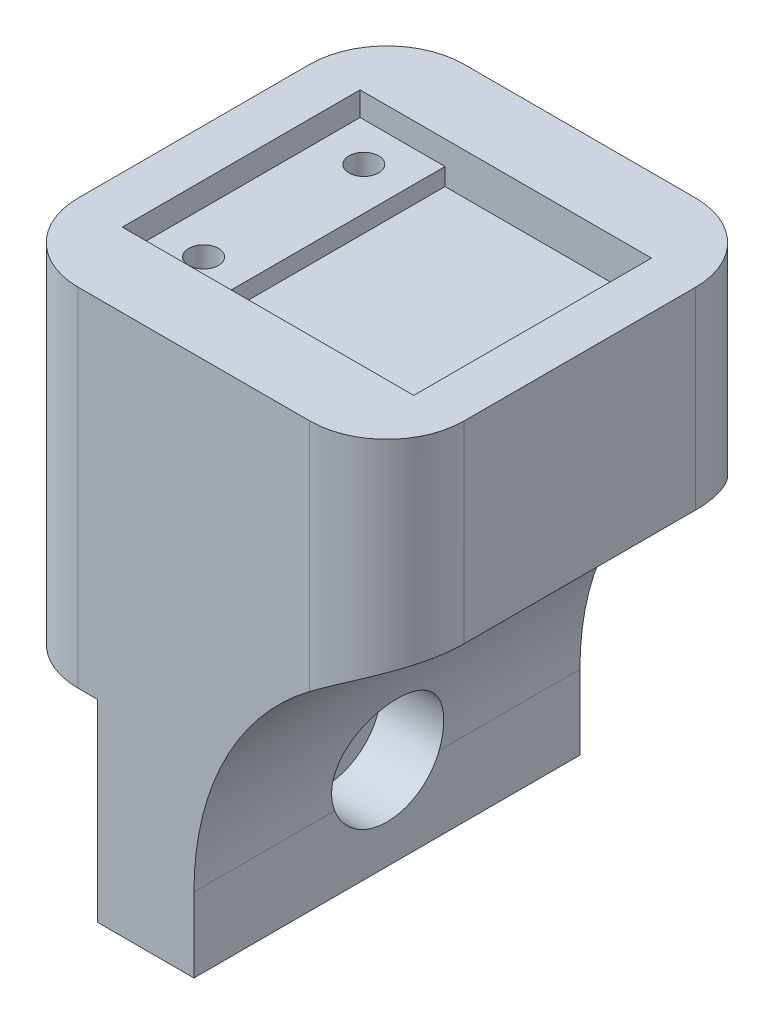
SolidWorks part; units mm, degrees
ref_plane "Front Plane" through (0, 0, 0) normal (0, 0, 1) x (1, 0, 0)
ref_plane "Top Plane" through (0, 0, 0) normal (0, 1, 0) x (1, 0, 0)
ref_plane "Right Plane" through (0, 0, 0) normal (1, 0, 0) x (0, 0, -1)
sketch "Profile" plane through (0, 0, 0) normal (0, 0, 1) x (1, 0, 0)
  line L1 (-6.35, 22.86) -> (6.35, 22.86)
  line L2 (-6.35, 22.86) -> (-6.35, 0)
  line L3 (-6.35, 0) -> (6.35, 0)
  line L4 (6.35, 22.86) -> (6.35, 0)
  line L5 (0, 0) -> (6.35, 0)
  line L6 (0, 0) -> (0, -12.7)
  line L7 (0, -12.7) -> (6.35, -12.7)
  line L8 (6.35, 0) -> (6.35, -12.7)
  dimension "D1" = 22.86
  dimension "D2" = 12.7
  dimension "D3" = 6.35
  dimension "D4" = 12.7
extrude "Boss-Extrude1" add sketch "Profile" along normal mid plane 25.4 contours L4 L1 L2 L3 | L8 L3 L6 L7 region at (0, 11.43, 0) region at (3.175, -6.35, 0)
sketch "ScrewHole" plane through (0, 0, 0) normal (-1, 0, 0) x (0, 0, 1)
  line L1 (12.7, -12.7) -> (-12.7, -12.7) construction
  line L2 (12.7, 0) -> (-12.7, 0) construction
  circle A0 centre (0, -6.477) radius 2.159
  point P2 (0, 0)
  point P10 (0, -12.7)
  dimension "D1" = 4.318
  dimension "D2" = 6.477
extrude "Cut-Extrude1" cut sketch "ScrewHole" against normal through all both
sketch "Sketch3" plane through (6.35, 0, 0) normal (1, 0, 0) x (0, 0, -1)
  circle A0 centre (0, -6.477) radius 2.159 construction
  circle A1 centre (0, -6.477) radius 2.159
  circle A2 centre (0, -6.477) radius 3.683
  dimension "D1" = 7.366
extrude "Cut-Extrude2" cut sketch "Sketch3" against normal blind 4.064
sketch "Sketch4" plane through (6.35, 0, 0) normal (1, 0, 0) x (0, 0, -1)
  line L0 (12.7, 22.86) -> (12.7, -12.7) construction
  line L1 (-12.7, 22.86) -> (12.7, 22.86)
  line L2 (-12.7, 22.86) -> (-12.7, 10.16)
  line L3 (-12.7, 10.16) -> (12.7, 10.16)
  line L4 (12.7, 22.86) -> (12.7, 10.16)
  dimension "D1" = 12.7
extrude "Boss-Extrude2" add sketch "Sketch4" along normal blind 12.7
sketch "Sketch6" plane through (0, 22.86, 0) normal (0, 1, 0) x (1, 0, 0)
  line L0 (-6.35, -12.7) -> (-6.35, 12.7) construction
  line L1 (-3.2385, 7.8232) -> (15.9385, 7.8232)
  line L2 (-3.2385, 7.8232) -> (-3.2385, -7.8232)
  line L3 (-3.2385, -7.8232) -> (15.9385, -7.8232)
  line L4 (15.9385, 7.8232) -> (15.9385, -7.8232)
  line L5 (-6.35, -12.7) -> (19.05, -12.7) construction
  point P6 (-6.35, 0)
  point P7 (-3.2385, 0)
  point P10 (6.35, -12.7)
  point P11 (6.35, -7.8232)
  dimension "D1" = 19.177
  dimension "D2" = 15.6464
extrude "Cut-Extrude3" cut sketch "Sketch6" against normal blind 1.5748
sketch "Sketch7" plane through (0, 21.2852, 0) normal (0, 1, 0) x (1, 0, 0)
  line L0 (13.1445, 5.2705) -> (13.1445, -5.2705) construction
  line L1 (15.9385, -7.8232) -> (15.9385, 7.8232) construction
  line L2 (6.35, 7.8232) -> (6.35, -7.8232) construction
  line L3 (15.9385, 7.8232) -> (-3.2385, 7.8232) construction
  line L4 (-3.2385, -7.8232) -> (15.9385, -7.8232) construction
  circle A0 centre (13.1445, 5.2705) radius 0.9779
  circle A1 centre (13.1445, -5.2705) radius 0.9779
  circle A2 centre (-0.4445, -5.2705) radius 0.9779
  circle A3 centre (-0.4445, 5.2705) radius 0.9779
  point P6 (15.9385, 0)
  point P7 (13.1445, 0)
  dimension "D3" = 1.9558
  dimension "D4" = 1.9558
  dimension "D1" = 10.541
  dimension "D2" = 2.794
ref_plane "Plane1" through (6.35, 0, 0) normal (1, 0, 0) x (0, 0, -1)
sketch "Sketch9" plane through (0, 21.2852, 0) normal (0, 1, 0) x (1, 0, 0)
  line L0 (-3.2385, -7.8232) -> (15.9385, -7.8232) construction
  line L1 (2.3495, 7.8232) -> (15.9385, 7.8232)
  line L2 (2.3495, 7.8232) -> (2.3495, -7.8232)
  line L3 (2.3495, -7.8232) -> (15.9385, -7.8232)
  line L4 (15.9385, 7.8232) -> (15.9385, -7.8232)
  line L7 (15.9385, -7.8232) -> (15.9385, 7.8232) construction
  line L8 (-3.2385, 7.8232) -> (-3.2385, -7.8232) construction
  line L9 (15.9385, 7.8232) -> (-3.2385, 7.8232) construction
  dimension "D1" = 5.588
extrude "Cut-Extrude5" cut sketch "Sketch9" against normal blind 1.143
extrude "Cut-Extrude6" cut sketch "Sketch7" against normal blind 12.7 contours A2 | A3
fillet "Fillet1" radius 19.05 1 edges at (6.35, 10.16, 0)
fillet "Fillet2" radius 5.08 4 edges at (-6.35, 11.43, -12.7) (19.05, 16.51, -12.7) (-6.35, 11.43, 12.7) (19.05, 16.51, 12.7)
